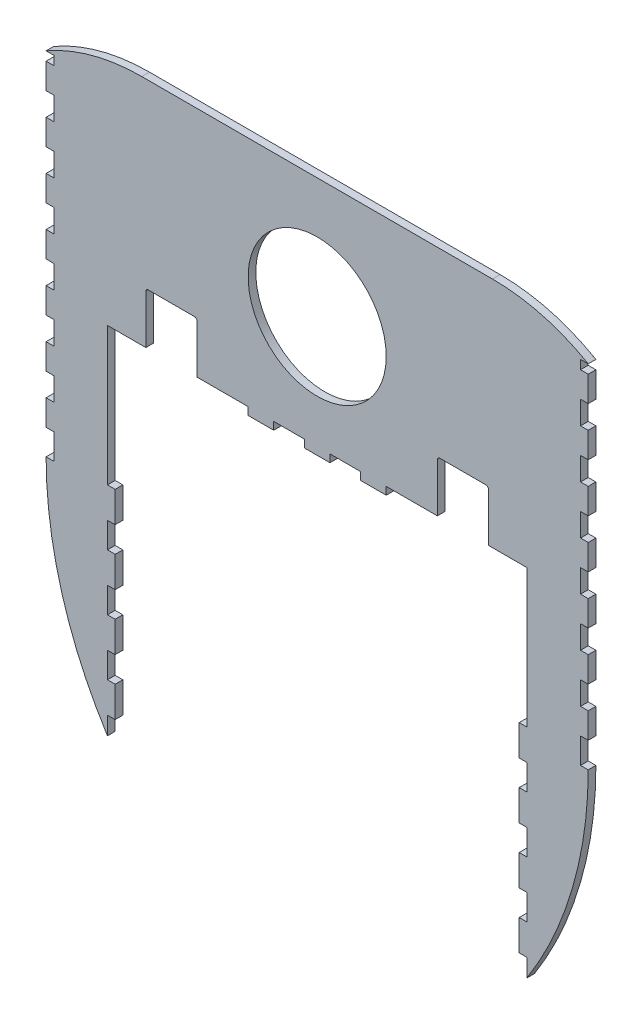
SolidWorks part; units mm, degrees
material "birch 3mm plywood"
ref_plane "Front" through (0, 0, 0) normal (0, 0, 1) x (1, 0, 0)
ref_plane "Top" through (0, 0, 0) normal (0, 1, 0) x (1, 0, 0)
ref_plane "Right" through (0, 0, 0) normal (1, 0, 0) x (0, 0, -1)
sketch "Sketch1" plane through (0, 0, 0) normal (0, 0, 1) x (1, 0, 0)
  line L0 (-106, 22.7408) -> (-106, 12.7408) construction
  line L1 (-82, 59.2408) -> (-82, 25.2408)
  line L2 (-103, 150.2408) -> (-106, 150.2408) construction
  line L3 (-103, 12.7408) -> (-106, 12.7408) construction
  line L4 (-103, 150.2408) -> (-103, 12.7408) construction
  line L5 (-47, 69.2408) -> (-27, 69.2408)
  line L6 (-82, 59.2408) -> (-82, 69.2408)
  line L7 (-103, 150.2408) -> (-106, 150.2408)
  line L8 (-103, 12.7408) -> (-106, 12.7408)
  line L9 (-103, 150.2408) -> (-103, 146.7408)
  line L10 (0, 0) -> (0, 66.2408) construction
  line L11 (-82, -69.7592) -> (-82, -62.7592)
  line L12 (-68.5834, 160.2408) -> (68.5834, 160.2408)
  line L14 (-47, 70.7408) -> (-47, 88.2408) construction
  line L15 (-48, 89.2408) -> (-66, 89.2408) construction
  line L16 (-67, 88.2408) -> (-67, 70.7408) construction
  line L17 (-82, 37.2408) -> (-82, 47.2408)
  line L18 (-47, 69.2408) -> (-47, 88.2408)
  line L19 (-48, 89.2408) -> (-66, 89.2408)
  line L20 (-67, 88.2408) -> (-67, 69.2408)
  line L22 (-103, 22.7408) -> (-106, 22.7408)
  line L24 (-103, 32.7408) -> (-106, 32.7408)
  line L25 (-106, 22.7408) -> (-106, 32.7408)
  line L26 (-103, 41.7408) -> (-106, 41.7408)
  line L27 (-106, 41.7408) -> (-106, 51.7408)
  line L28 (-103, 51.7408) -> (-106, 51.7408)
  line L30 (-103, 60.7408) -> (-106, 60.7408)
  line L31 (-106, 60.7408) -> (-106, 70.7408)
  line L32 (-103, 70.7408) -> (-106, 70.7408)
  line L34 (-103, 79.7408) -> (-106, 79.7408)
  line L35 (-106, 79.7408) -> (-106, 89.7408)
  line L36 (-103, 89.7408) -> (-106, 89.7408)
  line L38 (-103, 98.7408) -> (-106, 98.7408)
  line L39 (-106, 98.7408) -> (-106, 108.7408)
  line L40 (-103, 108.7408) -> (-106, 108.7408)
  line L42 (-103, 117.7408) -> (-106, 117.7408)
  line L43 (-106, 117.7408) -> (-106, 127.7408)
  line L44 (-103, 127.7408) -> (-106, 127.7408)
  line L46 (-103, 136.7408) -> (-106, 136.7408)
  line L47 (-106, 136.7408) -> (-106, 146.7408)
  line L48 (-103, 146.7408) -> (-106, 146.7408)
  line L49 (-103, 136.7408) -> (-103, 127.7408)
  line L50 (-103, 117.7408) -> (-103, 108.7408)
  line L51 (-103, 98.7408) -> (-103, 89.7408)
  line L52 (-103, 79.7408) -> (-103, 70.7408)
  line L53 (-103, 60.7408) -> (-103, 51.7408)
  line L54 (-103, 41.7408) -> (-103, 32.7408)
  line L55 (-103, 22.7408) -> (-103, 12.7408)
  line L56 (-82, 69.2408) -> (-67, 69.2408)
  line L57 (-82, 15.2408) -> (-82, 25.2408)
  line L58 (-82, -6.7592) -> (-82, 3.2408)
  line L59 (-82, -28.7592) -> (-82, -18.7592)
  line L60 (-17, 69.2408) -> (-5, 69.2408)
  line L61 (-82, -50.7592) -> (-82, -40.7592)
  line L62 (106, 22.7408) -> (106, 12.7408) construction
  line L63 (79, -18.7592) -> (82, -18.7592)
  line L64 (79, -6.7592) -> (79, -18.7592)
  line L65 (82, -6.7592) -> (79, -6.7592)
  line L66 (82, 3.2408) -> (82, -6.7592)
  line L67 (79, 3.2408) -> (82, 3.2408)
  line L68 (79, 15.2408) -> (79, 3.2408)
  line L69 (82, 15.2408) -> (79, 15.2408)
  line L70 (82, 25.2408) -> (82, 15.2408)
  line L71 (0, 160.2408) -> (0, 66.2408) construction
  line L74 (82, 47.2408) -> (82, 37.2408)
  line L78 (82, 69.2408) -> (82, 59.2408)
  line L79 (67, 69.2408) -> (82, 69.2408)
  line L80 (-82, -18.7592) -> (-82, -28.7592)
  line L81 (-82, -28.7592) -> (-79, -28.7592)
  line L82 (-79, -28.7592) -> (-79, -40.7592)
  line L83 (-79, -40.7592) -> (-82, -40.7592)
  line L84 (-82, -40.7592) -> (-82, -50.7592)
  line L85 (-82, -50.7592) -> (-79, -50.7592)
  line L86 (-79, -50.7592) -> (-79, -62.7592)
  line L87 (-79, -62.7592) -> (-82, -62.7592)
  line L88 (-82, -62.7592) -> (-82, -69.7592)
  line L89 (-82, -69.7592) -> (82, -69.7592)
  line L90 (82, -69.7592) -> (82, -62.7592)
  line L91 (82, -62.7592) -> (79, -62.7592)
  line L92 (79, -62.7592) -> (79, -50.7592)
  line L93 (79, -50.7592) -> (82, -50.7592)
  line L94 (82, -50.7592) -> (82, -40.7592)
  line L95 (82, -40.7592) -> (79, -40.7592)
  line L96 (79, -40.7592) -> (79, -28.7592)
  line L97 (79, -28.7592) -> (82, -28.7592)
  line L98 (82, -28.7592) -> (82, -18.7592)
  line L99 (82, -18.7592) -> (79, -18.7592)
  line L100 (79, -18.7592) -> (79, -6.7592)
  line L101 (79, -6.7592) -> (82, -6.7592)
  line L102 (82, -6.7592) -> (82, 3.2408)
  line L103 (82, 3.2408) -> (79, 3.2408)
  line L104 (79, 3.2408) -> (79, 15.2408)
  line L105 (79, 15.2408) -> (82, 15.2408)
  line L106 (82, 15.2408) -> (82, 25.2408)
  line L107 (82, 25.2408) -> (79, 25.2408)
  line L108 (79, 25.2408) -> (79, 37.2408)
  line L109 (79, 37.2408) -> (82, 37.2408)
  line L110 (82, 37.2408) -> (82, 47.2408)
  line L111 (82, 47.2408) -> (79, 47.2408)
  line L112 (79, 47.2408) -> (79, 59.2408)
  line L113 (79, 59.2408) -> (82, 59.2408)
  line L114 (82, 59.2408) -> (82, 69.2408)
  line L115 (82, 69.2408) -> (71, 69.2408)
  line L116 (71, 69.2408) -> (71, 66.2408)
  line L117 (71, 66.2408) -> (61, 66.2408)
  line L118 (61, 66.2408) -> (61, 69.2408)
  line L119 (61, 69.2408) -> (49, 69.2408)
  line L120 (49, 69.2408) -> (49, 66.2408)
  line L121 (49, 66.2408) -> (39, 66.2408)
  line L122 (39, 66.2408) -> (39, 69.2408)
  line L123 (39, 69.2408) -> (27, 69.2408)
  line L124 (27, 69.2408) -> (27, 66.2408)
  line L125 (27, 66.2408) -> (17, 66.2408)
  line L126 (17, 66.2408) -> (17, 69.2408)
  line L127 (17, 69.2408) -> (5, 69.2408)
  line L128 (5, 69.2408) -> (5, 66.2408)
  line L129 (5, 66.2408) -> (-5, 66.2408)
  line L130 (-5, 66.2408) -> (-5, 69.2408)
  line L131 (-5, 69.2408) -> (-17, 69.2408)
  line L132 (-17, 69.2408) -> (-17, 66.2408)
  line L133 (-17, 66.2408) -> (-27, 66.2408)
  line L134 (-27, 66.2408) -> (-27, 69.2408)
  line L135 (-27, 69.2408) -> (-39, 69.2408)
  line L136 (-39, 69.2408) -> (-39, 66.2408)
  line L137 (-39, 66.2408) -> (-49, 66.2408)
  line L138 (-49, 66.2408) -> (-49, 69.2408)
  line L139 (-49, 69.2408) -> (-61, 69.2408)
  line L140 (-61, 69.2408) -> (-61, 66.2408)
  line L141 (-61, 66.2408) -> (-71, 66.2408)
  line L142 (-71, 66.2408) -> (-71, 69.2408)
  line L143 (-71, 69.2408) -> (-82, 69.2408)
  line L144 (-82, 69.2408) -> (-82, 59.2408)
  line L145 (-82, 59.2408) -> (-79, 59.2408)
  line L146 (-79, 59.2408) -> (-79, 47.2408)
  line L147 (-79, 47.2408) -> (-82, 47.2408)
  line L148 (-82, 47.2408) -> (-82, 37.2408)
  line L149 (-82, 37.2408) -> (-79, 37.2408)
  line L150 (-79, 37.2408) -> (-79, 25.2408)
  line L151 (-79, 25.2408) -> (-82, 25.2408)
  line L152 (-82, 25.2408) -> (-82, 15.2408)
  line L153 (-82, 15.2408) -> (-79, 15.2408)
  line L154 (-79, 15.2408) -> (-79, 3.2408)
  line L155 (-79, 3.2408) -> (-82, 3.2408)
  line L156 (-82, 3.2408) -> (-82, -6.7592)
  line L157 (-82, -6.7592) -> (-79, -6.7592)
  line L158 (-79, -6.7592) -> (-79, -18.7592)
  line L159 (-79, -18.7592) -> (-82, -18.7592)
  line L160 (-82, -18.7592) -> (-82, -28.7592)
  line L161 (-82, -28.7592) -> (-79, -28.7592)
  line L162 (-79, -28.7592) -> (-79, -40.7592)
  line L163 (-79, -40.7592) -> (-82, -40.7592)
  line L164 (-82, -40.7592) -> (-82, -50.7592)
  line L165 (-82, -50.7592) -> (-79, -50.7592)
  line L166 (-79, -50.7592) -> (-79, -62.7592)
  line L167 (-79, -62.7592) -> (-82, -62.7592)
  line L168 (-82, -62.7592) -> (-82, -69.7592)
  line L209 (5, 66.2408) -> (-5, 66.2408)
  line L210 (-5, 66.2408) -> (-5, 69.2408)
  line L211 (-5, 69.2408) -> (-17, 69.2408)
  line L212 (-17, 69.2408) -> (-17, 66.2408)
  line L213 (-17, 66.2408) -> (-27, 66.2408)
  line L214 (-27, 66.2408) -> (-27, 69.2408)
  line L215 (-27, 69.2408) -> (-47, 69.2408)
  line L223 (-67, 69.2408) -> (-82, 69.2408)
  line L224 (-82, 69.2408) -> (-82, 59.2408)
  line L228 (-82, 47.2408) -> (-82, 37.2408)
  line L232 (-82, 25.2408) -> (-82, 15.2408)
  line L233 (-82, 15.2408) -> (-79, 15.2408)
  line L234 (-79, 15.2408) -> (-79, 3.2408)
  line L235 (-79, 3.2408) -> (-82, 3.2408)
  line L236 (-82, 3.2408) -> (-82, -6.7592)
  line L237 (-82, -6.7592) -> (-79, -6.7592)
  line L238 (-79, -6.7592) -> (-79, -18.7592)
  line L239 (-79, -18.7592) -> (-82, -18.7592)
  line L240 (27, 69.2408) -> (47, 69.2408)
  line L241 (27, 66.2408) -> (27, 69.2408)
  line L242 (17, 66.2408) -> (27, 66.2408)
  line L243 (17, 69.2408) -> (17, 66.2408)
  line L244 (5, 69.2408) -> (17, 69.2408)
  line L245 (5, 66.2408) -> (5, 69.2408)
  line L246 (82, -62.7592) -> (82, -69.7592)
  line L247 (79, -62.7592) -> (82, -62.7592)
  line L248 (79, -50.7592) -> (79, -62.7592)
  line L249 (82, -50.7592) -> (79, -50.7592)
  line L250 (82, -40.7592) -> (82, -50.7592)
  line L251 (79, -40.7592) -> (82, -40.7592)
  line L252 (79, -28.7592) -> (79, -40.7592)
  line L253 (82, -28.7592) -> (79, -28.7592)
  line L254 (82, -18.7592) -> (82, -28.7592)
  line L255 (82, -50.7592) -> (82, -40.7592)
  line L256 (17, 69.2408) -> (5, 69.2408)
  line L257 (82, -28.7592) -> (82, -18.7592)
  line L258 (82, -6.7592) -> (82, 3.2408)
  line L259 (82, 15.2408) -> (82, 25.2408)
  line L260 (82, 69.2408) -> (67, 69.2408)
  line L261 (103, 22.7408) -> (103, 12.7408)
  line L262 (103, 41.7408) -> (103, 32.7408)
  line L263 (103, 60.7408) -> (103, 51.7408)
  line L264 (103, 79.7408) -> (103, 70.7408)
  line L265 (103, 98.7408) -> (103, 89.7408)
  line L266 (103, 117.7408) -> (103, 108.7408)
  line L267 (103, 136.7408) -> (103, 127.7408)
  line L268 (103, 146.7408) -> (106, 146.7408)
  line L269 (106, 136.7408) -> (106, 146.7408)
  line L270 (103, 136.7408) -> (106, 136.7408)
  line L271 (103, 127.7408) -> (106, 127.7408)
  line L272 (106, 117.7408) -> (106, 127.7408)
  line L273 (103, 117.7408) -> (106, 117.7408)
  line L274 (103, 108.7408) -> (106, 108.7408)
  line L275 (106, 98.7408) -> (106, 108.7408)
  line L276 (103, 98.7408) -> (106, 98.7408)
  line L277 (103, 89.7408) -> (106, 89.7408)
  line L278 (106, 79.7408) -> (106, 89.7408)
  line L279 (103, 79.7408) -> (106, 79.7408)
  line L280 (103, 70.7408) -> (106, 70.7408)
  line L281 (106, 60.7408) -> (106, 70.7408)
  line L282 (103, 60.7408) -> (106, 60.7408)
  line L283 (103, 51.7408) -> (106, 51.7408)
  line L284 (106, 41.7408) -> (106, 51.7408)
  line L285 (103, 41.7408) -> (106, 41.7408)
  line L286 (106, 22.7408) -> (106, 32.7408)
  line L287 (103, 32.7408) -> (106, 32.7408)
  line L288 (103, 22.7408) -> (106, 22.7408)
  line L289 (67, 88.2408) -> (67, 69.2408)
  line L290 (48, 89.2408) -> (66, 89.2408)
  line L291 (47, 69.2408) -> (47, 88.2408)
  line L292 (82, 37.2408) -> (82, 47.2408)
  line L293 (82, -69.7592) -> (82, -62.7592)
  line L294 (103, 150.2408) -> (103, 146.7408)
  line L295 (103, 12.7408) -> (106, 12.7408)
  line L296 (103, 150.2408) -> (106, 150.2408)
  line L297 (82, 59.2408) -> (82, 69.2408)
  line L298 (47, 69.2408) -> (27, 69.2408)
  line L299 (0, 160.2408) -> (0, 189.65) construction
  line L300 (-82, 25.2408) -> (-82, 59.2408)
  line L301 (82, 15.2408) -> (82, 59.2408)
  arc A0 (-68.5834, 160.2408) -> (-106, 150.2408) centre (-68.5834, 85.2408) ccw
  arc A1 (-106, 12.7408) -> (-82, -69.7592) centre (47.7969, 12.7408) ccw
  arc A2 (-47, 88.2408) -> (-48, 89.2408) centre (-48, 88.2408) ccw construction
  arc A3 (-66, 89.2408) -> (-67, 88.2408) centre (-66, 88.2408) ccw construction
  arc A4 (-47, 88.2408) -> (-48, 89.2408) centre (-48, 88.2408) ccw
  arc A5 (-66, 89.2408) -> (-67, 88.2408) centre (-66, 88.2408) ccw
  arc A6 (66, 89.2408) -> (67, 88.2408) centre (66, 88.2408) cw
  arc A7 (47, 88.2408) -> (48, 89.2408) centre (48, 88.2408) cw
  arc A8 (106, 12.7408) -> (82, -69.7592) centre (-47.7969, 12.7408) cw
  arc A9 (68.5834, 160.2408) -> (106, 150.2408) centre (68.5834, 85.2408) cw
  circle A10 centre (0, 113.2408) radius 27
  dimension "D8" = 75
  dimension "D9" = 20
  dimension "D2" = 10
  dimension "D3" = 3
  dimension "D4" = 10
  dimension "D5" = 10
  dimension "D7" = 9
  dimension "D1" = 0
  dimension "D6" = 7
extrude "Boss-Extrude1" add sketch "Sketch1" along normal blind 3 contours A5 L19 A4 L18 L5 L214 L213 L212 L60 L210 L209 L12 A0 L7 L9 L48 L47 L46 L49 L44 L43 L42 L50 L40 L39 L38 L51 L36 L35 L34 L52 L32 L31 L30 L53 L28 L27 L26 L54 L24 L25 L22 L55 L8 A1 L11 L167 L166 L165 L61 region at (-85.128, 53.2408, 0)
